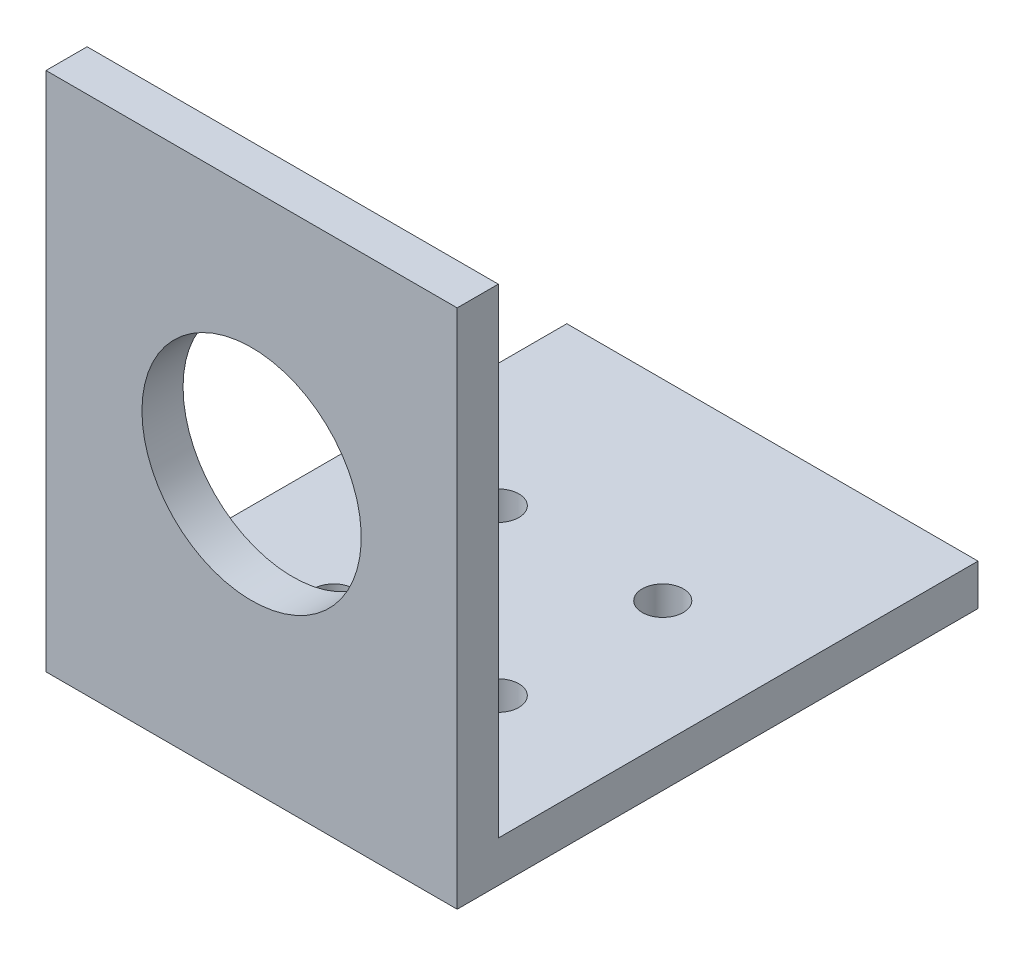
SolidWorks part; units mm, degrees
material "6063-O"
ref_plane "Front" through (0, 0, 0) normal (0, 0, 1) x (1, 0, 0)
ref_plane "Top" through (0, 0, 0) normal (0, 1, 0) x (1, 0, 0)
ref_plane "Right" through (0, 0, 0) normal (1, 0, 0) x (0, 0, -1)
sketch "草图1" plane through (0, 0, 0) normal (1, 0, 0) x (0, 0, -1)
  line L0 (0, 0) -> (0, 38)
  line L1 (0, 38) -> (3, 38)
  line L2 (3, 38) -> (3, 3)
  line L3 (3, 3) -> (38, 3)
  line L4 (38, 3) -> (38, 0)
  line L5 (38, 0) -> (0, 0)
  dimension "D1" = 38
  dimension "D2" = 3
  dimension "D3" = 35
  dimension "D4" = 35
extrude "凸台-拉伸1" add sketch "草图1" along normal blind 20
ref_plane "基准面1" through (20, 3, -38) normal (-1, 0, 0) x (0, 0, 1)
sketch "草图3" plane through (0, 3, 0) normal (0, 1, 0) x (1, 0, 0)
  line L0 (10, 38) -> (10, 0) construction
  line L1 (20, 38) -> (0, 38) construction
  line L2 (20, 0) -> (0, 0) construction
  circle A0 centre (16, 12) radius 1.5
  circle A1 centre (4, 12) radius 1.5
  circle A2 centre (4, 24) radius 1.5
  circle A3 centre (16, 24) radius 1.5
  dimension "D1" = 3
  dimension "D2" = 3
  dimension "D3" = 12
  dimension "D4" = 12
  dimension "D6" = 12
  dimension "D5" = 2
extrude "切除-拉伸1" cut sketch "草图3" against normal through all
sketch "草图5" plane through (0, 0, -3) normal (0, 0, -1) x (-1, 0, 0)
  line L0 (-10, 38) -> (-10, 0) construction
  line L1 (-20, 38) -> (0, 38) construction
  line L3 (-20, 0) -> (0, 0) construction
  circle A0 centre (-10, 20) radius 5
  dimension "D1" = 10
  dimension "D2" = 20
extrude "切除-拉伸3" cut sketch "草图5" against normal through all
sketch "草图8" plane through (0, 0, -3) normal (0, 0, -1) x (-1, 0, 0)
  circle A0 centre (-10, 20) radius 8
  dimension "D1" = 16
extrude "切除-拉伸4" cut sketch "草图8" against normal blind 10
sketch "草图9" plane through (20, 0, 0) normal (1, 0, 0) x (0, 0, -1)
  line L0 (0, 0) -> (38, 0) construction
  line L1 (0, 38) -> (3, 38)
  line L2 (0, 38) -> (0, 0)
  line L3 (0, 0) -> (3, 0)
  line L4 (3, 38) -> (3, 0)
  line L6 (3, 3) -> (38, 3)
  line L7 (3, 3) -> (3, 0)
  line L8 (3, 0) -> (38, 0)
  line L9 (38, 3) -> (38, 0)
  line M1 (0, 0) -> (38, 0)
  line M2 (38, 0) -> (38, 3)
  line M3 (38, 3) -> (3, 3)
  line M4 (3, 3) -> (3, 38)
  line M5 (3, 38) -> (0, 38)
  line M6 (0, 38) -> (0, 0)
extrude "凸台-拉伸2" add sketch "草图9" along normal blind 5 contours L4 M4 M5 M6 M1 | L4 M3 M1 M2 region at (20, 19, -1.5) region at (20, 1.5, -20.5)
sketch "草图10" plane through (0, 0, 0) normal (-1, 0, 0) x (0, 0, 1)
  line L1 (0, 38) -> (-3, 38)
  line L2 (0, 38) -> (0, 3)
  line L3 (0, 3) -> (-3, 3)
  line L4 (-3, 38) -> (-3, 3)
  line L5 (0, 3) -> (-38, 3)
  line L6 (0, 3) -> (0, 0)
  line L7 (0, 0) -> (-38, 0)
  line L8 (-38, 3) -> (-38, 0)
  line M1 (-38, 0) -> (0, 0)
  line M2 (0, 0) -> (0, 38)
  line M3 (0, 38) -> (-3, 38)
  line M4 (-3, 38) -> (-3, 3)
  line M5 (-3, 3) -> (-38, 3)
  line M6 (-38, 3) -> (-38, 0)
extrude "凸台-拉伸3" add sketch "草图10" along normal blind 5 contours L3 M2 M3 M4 | L3 M2 M5 M6 M1 region at (0, 20.5, -1.5) region at (0, 1.5, -19)
